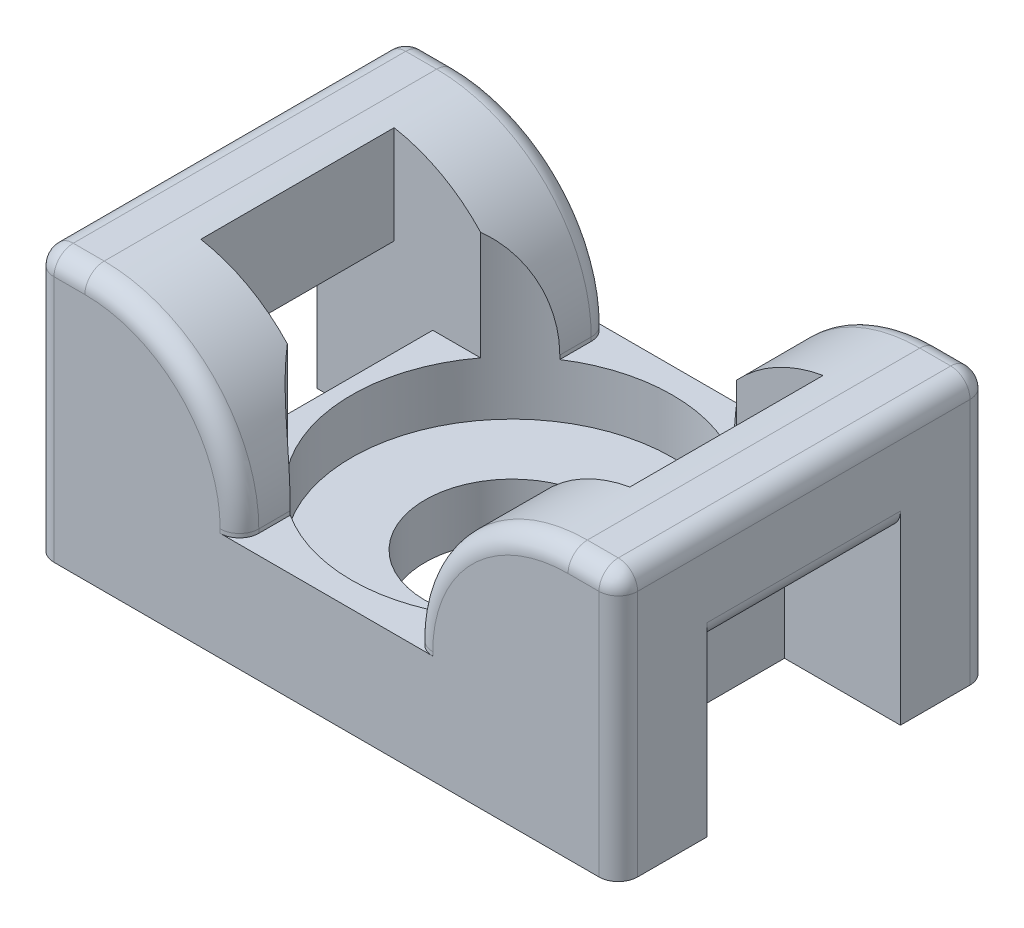
SolidWorks part; units mm, degrees
material "POM(White)"
ref_plane "Front Plane" through (0, 0, 0) normal (0, 0, 1) x (1, 0, 0)
ref_plane "Top Plane" through (0, 0, 0) normal (0, 1, 0) x (1, 0, 0)
ref_plane "Right Plane" through (0, 0, 0) normal (1, 0, 0) x (0, 0, -1)
sketch "Sketch1" plane through (0, 0, 0) normal (0, 1, 0) x (1, 0, 0)
  line L1 (-7.55, -4.8) -> (7.55, -4.8)
  line L2 (-7.55, -4.8) -> (-7.55, 4.8)
  line L3 (-7.55, 4.8) -> (7.55, 4.8)
  line L4 (7.55, -4.8) -> (7.55, 4.8)
  line L5 (-7.55, -4.8) -> (7.55, 4.8) construction
  line L6 (-7.55, 4.8) -> (7.55, -4.8) construction
  point P0 (0, 0)
  dimension "D1" = 15.1
  dimension "D2" = 9.6
extrude "Boss-Extrude1" add sketch "Sketch1" along normal blind 6.9
sketch "Sketch3" plane through (0, 6.9, 0) normal (0, 1, 0) x (1, 0, 0)
  circle A0 centre (0, 0) radius 2.25
  dimension "D1" = 4.5
extrude "Cut-Extrude1" cut sketch "Sketch3" against normal through all
sketch "Sketch4" plane through (0, 6.9, 0) normal (0, 1, 0) x (1, 0, 0)
  circle A0 centre (0, 0) radius 4.15
  dimension "D1" = 8.3
extrude "Cut-Extrude2" cut sketch "Sketch4" against normal offset from surface (5.5 mm away) 1.4 up to face at (0, 0, 2.25)
sketch "Sketch5" plane through (0, 6.9, 0) normal (0, 1, 0) x (1, 0, 0)
  line L0 (7.55, -4.8) -> (7.55, 4.8) construction
  line L1 (-7.55, -2.5) -> (7.55, -2.5)
  line L2 (-7.55, -2.5) -> (-7.55, 2.5)
  line L3 (-7.55, 2.5) -> (7.55, 2.5)
  line L4 (7.55, -2.5) -> (7.55, 2.5)
  line L5 (-7.55, -2.5) -> (7.55, 2.5) construction
  line L6 (-7.55, 2.5) -> (7.55, -2.5) construction
  point P0 (0, 0)
extrude "Cut-Extrude3" cut sketch "Sketch5" against normal offset from surface (4.1 mm away) 2.8 up to face at (0, 0, 2.25)
sketch "Sketch6" plane through (0, 0, 0) normal (0, 0, 1) x (1, 0, 0)
  line L0 (-7.55, 0) -> (7.55, 0) construction
  line L1 (-4.8, 2.8) -> (4.8, 2.8) construction
  line L2 (-4.8, 2.8) -> (-4.8, 0) construction
  line L3 (-4.8, 0) -> (4.8, 0) construction
  line L4 (4.8, 2.8) -> (4.8, 0) construction
  line L5 (-7.55, 2.8) -> (-3.3125, 2.8) construction
  line L6 (0, 6.9) -> (0, 2.8) construction
  line L7 (-7.55, 6.9) -> (7.55, 6.9) construction
  line L9 (-2.25, 2.8) -> (2.25, 2.8)
  line L10 (-2.25, 2.8) -> (-2.25, 6.9)
  line L11 (-2.25, 6.9) -> (2.25, 6.9)
  line L12 (2.25, 6.9) -> (2.25, 2.8)
  dimension "D1" = 9.6
  dimension "D2" = 4.5
extrude "Cut-Extrude4" cut sketch "Sketch6" against normal mid plane 22.8
sketch "Sketch9" plane through (-7.55, 0, 0) normal (-1, 0, 0) x (0, 0, 1)
  line L0 (-4.8, 0) -> (4.8, 0) construction
  line L1 (-2.5, 2.8) -> (2.5, 2.8)
  line L2 (-2.5, 2.8) -> (-2.5, 0)
  line L3 (-2.5, 0) -> (2.5, 0)
  line L4 (2.5, 2.8) -> (2.5, 0)
extrude "Cut-Extrude5" cut sketch "Sketch9" against normal blind 3
fillet "Fillet3" radius 0.5 4 edges at (7.55, 3.45, -4.8) (7.55, 3.45, 4.8) (-7.55, 3.45, 4.8) (-7.55, 3.45, -4.8)
sketch "Sketch10" plane through (0, 0, -2.5) normal (0, 0, 1) x (1, 0, 0)
  line L0 (-4.55, 2.8) -> (-3.3125, 2.8) construction
  line L1 (-7.55, 6.9) -> (-5.55, 6.9)
  line L2 (-7.55, 6.9) -> (-7.55, 4.3)
  line L3 (-7.55, 4.3) -> (-5.55, 4.3)
  line L4 (-5.55, 6.9) -> (-5.55, 4.3)
  dimension "D2" = 2
  dimension "D1" = 1.5
extrude "Boss-Extrude2" add sketch "Sketch10" along normal up to next
mirror "Mirror1" about plane through (0, 0, 0) normal (1, 0, 0) of "Cut-Extrude5", "Boss-Extrude2"
fillet "Fillet4" radius 4 4 edges at (2.25, 6.9, -4.1436) (-2.25, 6.9, -4.1436) (-2.25, 6.9, 4.1436) (2.25, 6.9, 4.1436)
fillet "Fillet5" radius 0.5 18 edges at (2.25, 2.85, -4.8) (3.4216, 5.7284, -4.8) (6.65, 6.9, -4.8) (7.4036, 6.9, -4.6536) (7.55, 6.9, 0) (7.4036, 6.9, 4.6536) (6.65, 6.9, 4.8) (2.25, 2.85, 4.8) (-2.25, 2.85, 4.8) (-3.4216, 5.7284, 4.8) (-6.65, 6.9, 4.8) (-7.4036, 6.9, 4.6536) (-7.55, 6.9, 0) (-7.4036, 6.9, -4.6536) (-6.65, 6.9, -4.8) (-2.25, 2.85, -4.8) (3.4216, 5.7284, 4.8) (-3.4216, 5.7284, -4.8)
fillet "Fillet6" radius 0.5 2 edges at (-7.55, 4.3, 0) (7.55, 4.3, 0)
fillet "Fillet7" [suppressed] radius 0.5
fillet "Fillet8" [suppressed] radius 0.5
equation "\"D\"= 4.5mm"
equation "\"D1\"= 8.3mm"
equation "\"A\"= 15.1mm"
equation "\"B\"= 9.6mm"
equation "\"C\"= 5mm"
equation "\"E\"= 1.5mm"
equation "\"F\"= 1.4"
equation "\"H\"= 6.9mm"
equation "\"D1@Sketch1\"=\"A\""
equation "\"D2@Sketch1\"=\"B\""
equation "\"D1@Boss-Extrude1\"=\"H\""
equation "\"D1@Sketch3\"=\"D\""
equation "\"D1@Sketch4\"=\"D1\""
equation "\"D1@Cut-Extrude2\"=\"F\""
equation "\"D1@Sketch5\"=\"C\""
equation "\"D1@Cut-Extrude3\"=\"F\"*2"
equation "\"D1@Sketch6\"=\"B\""
equation "\"D1@Sketch10\"=\"E\""
